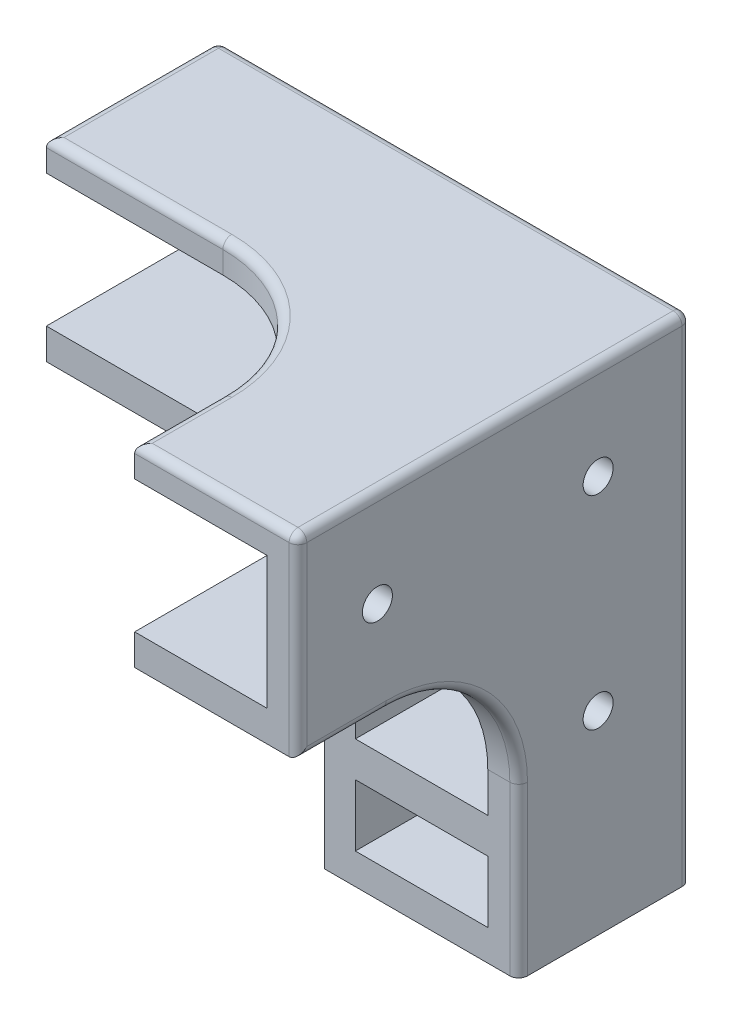
SolidWorks part; units mm, degrees
ref_plane "Front Plane" through (0, 0, 0) normal (0, 0, 1) x (1, 0, 0)
ref_plane "Top Plane" through (0, 0, 0) normal (0, 1, 0) x (1, 0, 0)
ref_plane "Right Plane" through (0, 0, 0) normal (1, 0, 0) x (0, 0, -1)
sketch "Sketch1" plane through (0, 0, 0) normal (0, 0, 1) x (1, 0, 0)
  line L1 (-5.6994, 32.9163) -> (16.3006, 32.9163)
  line L2 (-5.6994, 10.9163) -> (-5.6994, -23.0837)
  line L3 (-5.6994, -23.0837) -> (16.3006, -23.0837)
  line L4 (16.3006, 32.9163) -> (16.3006, -23.0837)
  line L5 (-5.6994, 10.9163) -> (-37.1994, 10.9163)
  line L7 (-5.6994, 32.9163) -> (-37.1994, 32.9163)
  line L8 (-37.1994, 10.9163) -> (-37.1994, 32.9163)
  dimension "D1" = 22
  dimension "D2" = 22
  dimension "D3" = 56
  dimension "D4" = 53.5
extrude "Boss-Extrude1" add sketch "Sketch1" along normal blind 19.5
sketch "Sketch3" plane through (0, 0, 19.5) normal (0, 0, 1) x (1, 0, 0)
  line L1 (16.3006, 32.9163) -> (-2.1994, 32.9163)
  line L2 (16.3006, 32.9163) -> (16.3006, 10.9163)
  line L3 (16.3006, 10.9163) -> (-2.1994, 10.9163)
  line L4 (-2.1994, 32.9163) -> (-2.1994, 10.9163)
  dimension "D1" = 18.5
  dimension "D2" = 22
extrude "Boss-Extrude2" add sketch "Sketch3" along normal blind 25
sketch "Sketch5" plane through (0, 0, 44.5) normal (0, 0, 1) x (1, 0, 0)
  line L0 (-37.1994, 32.9163) -> (-37.1994, 10.9163) construction
  line L1 (-37.1994, 29.4163) -> (12.8006, 29.4163)
  line L2 (-37.1994, 29.4163) -> (-37.1994, 14.4163)
  line L3 (-37.1994, 14.4163) -> (12.8006, 14.4163)
  line L4 (12.8006, 29.4163) -> (12.8006, 14.4163)
  line L5 (16.3006, 10.9163) -> (16.3006, 32.9163) construction
  line L6 (-2.1994, 6.4163) -> (12.8006, 6.4163)
  line L7 (-2.1994, 6.4163) -> (-2.1994, -8.5837)
  line L8 (-2.1994, -8.5837) -> (12.8006, -8.5837)
  line L9 (12.8006, 6.4163) -> (12.8006, -8.5837)
  line L12 (-2.1994, 32.9163) -> (-37.1994, 32.9163) construction
  line L13 (-2.1994, 10.9163) -> (16.3006, 10.9163) construction
  line L15 (16.3006, -23.0837) -> (16.3006, 10.9163) construction
  line L16 (-5.6994, -23.0837) -> (16.3006, -23.0837) construction
  line L17 (-2.1994, -12.5837) -> (12.8006, -12.5837)
  line L18 (-2.1994, -12.5837) -> (-2.1994, -19.5837)
  line L19 (-2.1994, -19.5837) -> (12.8006, -19.5837)
  line L20 (12.8006, -12.5837) -> (12.8006, -19.5837)
  dimension "D1" = 3.5
  dimension "D2" = 4.5
  dimension "D3" = 15
  dimension "D4" = 3.5
  dimension "D5" = 15
  dimension "D6" = 15
  dimension "D7" = 3.5
  dimension "D8" = 15
  dimension "D9" = 4
  dimension "D10" = 3.5
extrude "Cut-Extrude1" cut sketch "Sketch5" against normal offset from surface (40.5 mm away) 4 up to face at (-8.8661, 6.9163, 0)
sketch "Sketch7" plane through (16.3006, 0, 0) normal (1, 0, 0) x (0, 0, -1)
  line L0 (-34.5, 10.9163) -> (-19.5, 10.9163)
  line L1 (-44.5, 10.9163) -> (-19.5, 10.9163) construction
  line L2 (-19.5, 10.9163) -> (-19.5, -4.0837)
  line L3 (-19.5, -23.0837) -> (-19.5, 10.9163) construction
  arc A0 (-34.5, 10.9163) -> (-19.5, -4.0837) centre (-34.5, -4.0837) cw
  dimension "D1" = 15
extrude "Boss-Extrude4" add sketch "Sketch7" against normal blind 3.5
sketch "Sketch8" plane through (0, 0, 0) normal (0, 0, -1) x (-1, 0, 0)
  line L0 (5.6994, 10.9163) -> (20.6994, 10.9163)
  line L1 (37.1994, 10.9163) -> (5.6994, 10.9163) construction
  line L2 (5.6994, 10.9163) -> (5.6994, -4.0837)
  line L3 (5.6994, 10.9163) -> (5.6994, -23.0837) construction
  arc A0 (20.6994, 10.9163) -> (5.6994, -4.0837) centre (20.6994, -4.0837) ccw
  dimension "D1" = 15
extrude "Boss-Extrude5" add sketch "Sketch8" against normal blind 3.5
sketch "Sketch9" plane through (0, 32.9163, 0) normal (0, 1, 0) x (1, 0, 0)
  line L0 (-2.1994, -34.5) -> (-2.1994, -19.5)
  line L1 (-2.1994, -44.5) -> (-2.1994, -19.5) construction
  line L2 (-2.1994, -19.5) -> (-17.1994, -19.5)
  line L3 (-2.1994, -19.5) -> (-37.1994, -19.5) construction
  arc A0 (-2.1994, -34.5) -> (-17.1994, -19.5) centre (-17.1994, -34.5) ccw
  dimension "D1" = 15
extrude "Boss-Extrude6" add sketch "Sketch9" against normal blind 3.5
fillet "Fillet3" radius 3 1 edges
sketch "Sketch11" plane through (0, 0, 0) normal (0, 0, -1) x (-1, 0, 0)
  line L0 (1.1994, -23.0837) -> (1.1994, 10.9163) construction
  line L2 (5.6994, -23.0837) -> (-16.3006, -23.0837) construction
  line L5 (5.6994, -4.0837) -> (5.6994, -23.0837) construction
  text T0 "MR.3" font "Century Gothic" height 12
  dimension "D1" = 4.5
extrude "Cut-Extrude3" cut sketch "Sketch11" against normal blind 1
sketch "Sketch12" plane through (0, 0, 0) normal (0, 0, -1) x (-1, 0, 0)
  line L0 (37.1994, 21.9163) -> (-16.3006, 21.9163) construction
  line L1 (37.1994, 32.9163) -> (37.1994, 10.9163) construction
  line L2 (-16.3006, -23.0837) -> (-16.3006, 32.9163) construction
  line L3 (-12.8006, 14.4163) -> (-12.8006, 29.4163) construction
  circle A0 centre (-5.3006, 21.9163) radius 1.7
  circle A1 centre (10.9494, 21.9163) radius 1.7
  circle A2 centre (27.1994, 21.9163) radius 1.7
  dimension "D4" = 3.4
  dimension "D1" = 7.5
  dimension "D2" = 10
  dimension "D3" = 16.25
extrude "Cut-Extrude4" cut sketch "Sketch12" against normal blind 5
sketch "Sketch13" plane through (-5.6994, 0, 0) normal (-1, 0, 0) x (0, 0, 1)
  line L0 (4, 6.4163) -> (19.5, 6.4163) construction
  line L1 (19.5, 10.9163) -> (19.5, -23.0837) construction
  circle A0 centre (10.5, -1.0837) radius 1.7
  dimension "D2" = 9
  dimension "D3" = 3.4
  dimension "D1" = 7.5
extrude "Cut-Extrude5" cut sketch "Sketch13" against normal blind 45
sketch "Sketch14" plane through (16.3006, 0, 0) normal (1, 0, 0) x (0, 0, -1)
  line L0 (-10.5, -1.0837) -> (-10.5, 32.9163) construction
  line L1 (-44.5, 32.9163) -> (0, 32.9163) construction
  line L2 (-44.5, 21.9163) -> (-10.5, 21.9163) construction
  line L3 (-44.5, 10.9163) -> (-44.5, 32.9163) construction
  circle A0 centre (-10.5, 21.9163) radius 1.7
  circle A1 centre (-35.5, 21.9163) radius 1.7
  dimension "D1" = 3.4
  dimension "D2" = 9
extrude "Cut-Extrude6" cut sketch "Sketch14" against normal blind 45
sketch "Sketch15" plane through (0, -23.0837, 0) normal (0, -1, 0) x (1, 0, 0)
  line L0 (16.3006, 9.75) -> (-5.6994, 9.75) construction
  line L1 (16.3006, 19.5) -> (16.3006, 0) construction
  line L2 (-5.6994, 19.5) -> (-5.6994, 0) construction
  line L3 (5.3006, 19.5) -> (5.3006, 0) construction
  line L4 (-5.6994, 19.5) -> (16.3006, 19.5) construction
  line L5 (-5.6994, 0) -> (16.3006, 0) construction
  circle A0 centre (5.3006, 9.75) radius 1.7
  dimension "D1" = 3.4
extrude "Cut-Extrude7" cut sketch "Sketch15" against normal blind 4
fillet "Fillet4" radius 1 16 edges at (-28.9494, 10.9163, 0) (-10.0928, 6.5229, 0) (16.3006, 6.5229, 23.8934) (-6.5928, 32.9163, 23.8934) (-37.1994, 21.9163, 0) (-5.6994, -13.5837, 0) (-37.1994, 32.9163, 9.75) (-10.4494, 32.9163, 0) (7.0506, 32.9163, 44.5) (16.3006, 21.9163, 44.5) (16.3006, 32.9163, 22.25) (16.3006, 4.9163, 0)
